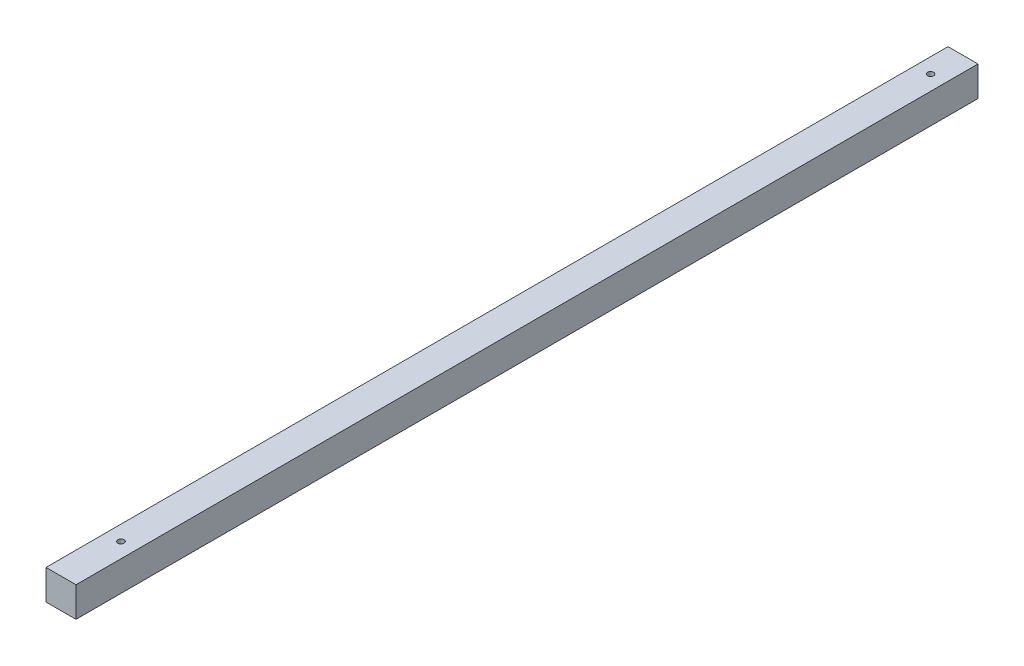
SolidWorks part; units mm, degrees
ref_plane "Plan de face" through (0, 0, 0) normal (0, 0, 1) x (1, 0, 0)
ref_plane "Plan de dessus" through (0, 0, 0) normal (0, 1, 0) x (1, 0, 0)
ref_plane "Plan de droite" through (0, 0, 0) normal (1, 0, 0) x (0, 0, -1)
sketch "Esquisse1" plane through (0, 0, 0) normal (0, 0, 1) x (1, 0, 0)
  line L1 (0, 0) -> (10, 0)
  line L2 (0, 0) -> (0, 10)
  line L3 (0, 10) -> (10, 10)
  line L4 (10, 0) -> (10, 10)
  dimension "D1" = 10
  dimension "D2" = 10
extrude "Boss.-Extru.1" add sketch "Esquisse1" along normal blind 300.81
sketch "Esquisse2" plane through (0, 10, 0) normal (0, 1, 0) x (1, 0, 0)
  line L0 (10, 0) -> (0, 0) construction
  line L1 (10, -300.81) -> (10, 0) construction
  circle A0 centre (5, -10.81) radius 1.025
  dimension "D1" = 2.05
  dimension "D2" = 10.81
  dimension "D3" = 5
extrude "Enlèv. mat.-Extru.1" cut sketch "Esquisse2" against normal through all contours A0
sketch "Esquisse3" plane through (0, 10, 0) normal (0, 1, 0) x (1, 0, 0)
  line L0 (10, -300.81) -> (0, -300.81) construction
  line L1 (0, -300.81) -> (0, 0) construction
  circle A0 centre (5, -280.81) radius 1.025
  dimension "D1" = 20
  dimension "D2" = 5
  dimension "D3" = 2.05
extrude "Enlèv. mat.-Extru.2" cut sketch "Esquisse3" against normal through all
